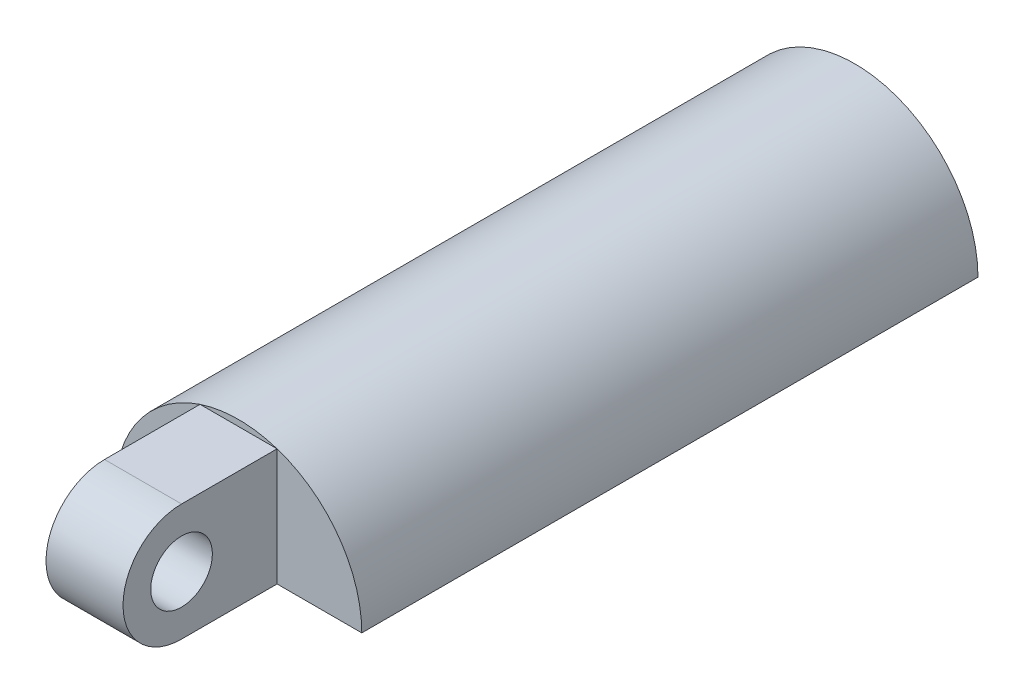
SolidWorks part; units mm, degrees
ref_plane "정면" through (0, 0, 0) normal (0, 0, 1) x (1, 0, 0)
ref_plane "윗면" through (0, 0, 0) normal (0, 1, 0) x (1, 0, 0)
ref_plane "우측면" through (0, 0, 0) normal (1, 0, 0) x (0, 0, -1)
sketch "스케치1" plane through (0, 0, 0) normal (0, 0, 1) x (1, 0, 0)
  line L5 (-8, 0) -> (8, 0)
  arc A0 (8, 0) -> (-8, 0) centre (0, 0) ccw
  arc A1 (4, 0) -> (-4, 0) centre (0, 0) ccw
  dimension "D1" = 8
  dimension "D2" = 4
extrude "보스-돌출1" add sketch "스케치1" along normal blind 40 contours A1 L5 A0 | L5 A1 region at (0, 7.8211, 0) region at (0, 1.6977, 0)
sketch "스케치4" plane through (0, 0, 40) normal (0, 0, 1) x (1, 0, 0)
  line L0 (-8, 0) -> (8, 0) construction
  line L1 (0, 0) -> (0, 8) construction
  arc A0 (8, 0) -> (-8, 0) centre (0, 0) ccw construction
sketch "스케치6" plane through (0, 0, 40) normal (0, 0, 1) x (1, 0, 0)
  line L0 (0, 0) -> (2.5, 0)
  line L1 (2.5, 0) -> (2.5, 7.5993)
  line L2 (0, 0) -> (-2.5, 0)
  line L3 (-2.5, 0) -> (-2.5, 7.5993)
  line L4 (-2.5, 7.5993) -> (2.5, 7.5993)
  arc A0 (8, 0) -> (-8, 0) centre (0, 0) ccw construction
  dimension "D1" = 2.5
  dimension "D2" = 2.5
extrude "보스-돌출2" add sketch "스케치6" along normal blind 10 contours L4 L1 L0 L2 L3
sketch "스케치8" plane through (2.5, 0, 0) normal (1, 0, 0) x (0, 0, -1)
  line L0 (-50, 3.7997) -> (-40, 3.7997) construction
  line L1 (-50, 0) -> (-50, 7.5993) construction
  line L2 (-40, 0) -> (-40, 7.5993) construction
  line L3 (-50, 0) -> (-40, 0) construction
  line L4 (-50, 3.7997) -> (-50, 0)
  line L5 (-50, 0) -> (-46.2003, 0)
  line L6 (-50, 3.7997) -> (-50, 7.5993)
  line L7 (-50, 7.5993) -> (-46.2003, 7.5993)
  circle A0 centre (-46.2003, 3.7997) radius 3.7997
  circle A1 centre (-46.2003, 3.7997) radius 2
  line M3 (-40, 7.5993) -> (-50, 7.5993)
  line M4 (-50, 7.5993) -> (-50, 0)
  line M5 (-50, 0) -> (-40, 0)
  dimension "D1" = 4
extrude "컷-돌출1" cut sketch "스케치8" against normal up to next contours A0 M3 M4 | A0 M4 M5 region at (2.5, 0.8487, 49.1513) region at (2.5, 6.7506, 49.1513)
extrude "컷-돌출2" cut sketch "스케치8<4>" against normal up to next contours A1 L0 | L0 A1 region at (2.5, 2.9508, 46.2003) region at (2.5, 4.6485, 46.2003)
sketch "스케치8<4>" plane through (2.5, 0, 0) normal (1, 0, 0) x (0, 0, -1) same geometry as "스케치8"
